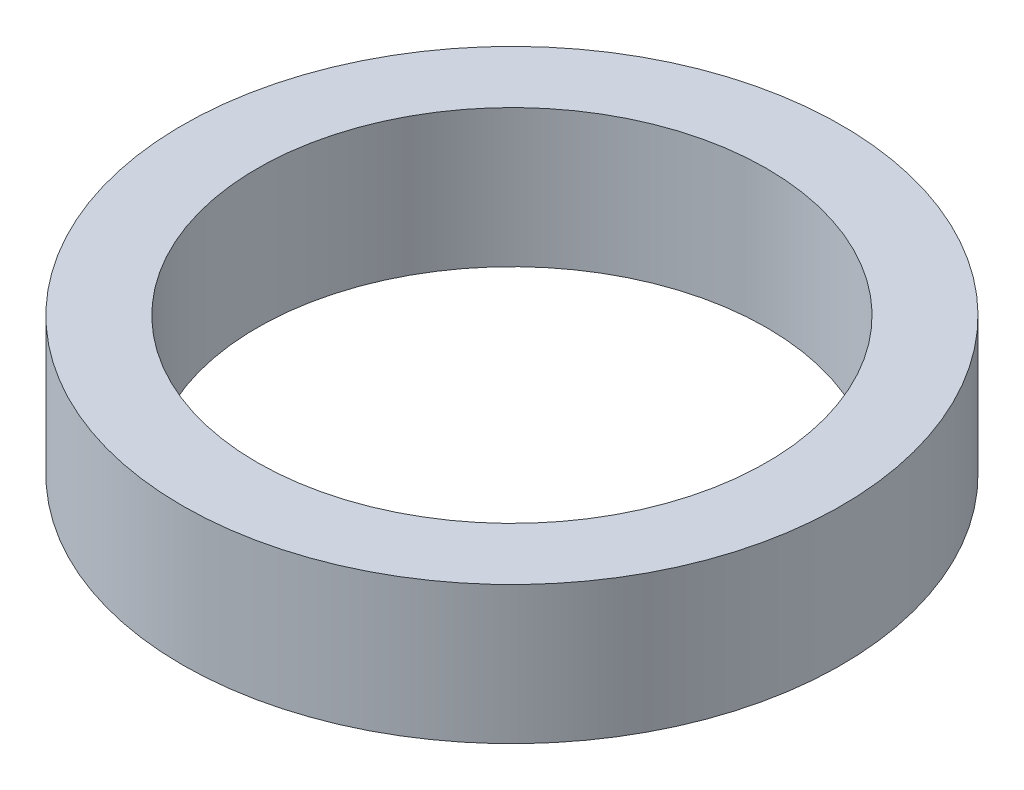
SolidWorks part; units mm, degrees
ref_plane "Front Plane" through (0, 0, 0) normal (0, 0, 1) x (1, 0, 0)
ref_plane "Top Plane" through (0, 0, 0) normal (0, 1, 0) x (1, 0, 0)
ref_plane "Right Plane" through (0, 0, 0) normal (1, 0, 0) x (0, 0, -1)
sketch "Sketch1" plane through (0, 0, 0) normal (0, 1, 0) x (1, 0, 0)
  circle A0 centre (0, 0) radius 55
  dimension "FLANGE_OD" = 110
extrude "Boss-Extrude1" add sketch "Sketch1" along normal blind 23
sketch "Sketch2" plane through (0, 0, 0) normal (0, 1, 0) x (1, 0, 0)
  circle A0 centre (0, 0) radius 42.5
  dimension "BORE_D" = 85
extrude "Cut-Extrude1" cut sketch "Sketch2" along normal through all
sketch "Sketch3" plane through (0, 23, 0) normal (0, 1, 0) x (1, 0, 0)
  circle A0 centre (0, 0) radius 24.7612 construction
  circle A1 centre (-24.7612, 0) radius 1.5015
  dimension "BOLT_D" = 3.0031
  dimension "BOLT_PCD" = 49.5224
extrude "Cut-Extrude2" cut sketch "Sketch3" against normal blind 15.491 rebuild error yes
pattern_circular "CirPattern1" count 3 over 360 rebuild error yes
